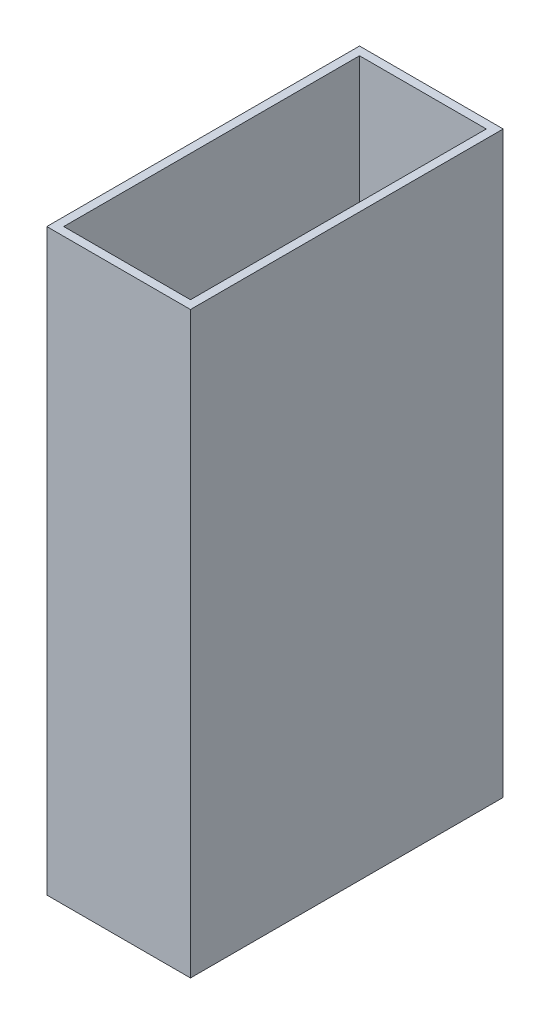
SolidWorks part; units mm, degrees
ref_plane "Plan de face" through (0, 0, 0) normal (0, 0, 1) x (1, 0, 0)
ref_plane "Plan de dessus" through (0, 0, 0) normal (0, 1, 0) x (1, 0, 0)
ref_plane "Plan de droite" through (0, 0, 0) normal (1, 0, 0) x (0, 0, -1)
sketch "Esquisse1" plane through (0, 0, 0) normal (0, 1, 0) x (1, 0, 0)
  line L0 (-17, 37) -> (17, 37)
  line L1 (-15, -35) -> (15, -35)
  line L2 (-15, -35) -> (-15, 35)
  line L3 (-15, 35) -> (15, 35)
  line L4 (15, -35) -> (15, 35)
  line L5 (-15, -35) -> (15, 35) construction
  line L6 (-15, 35) -> (15, -35) construction
  line L7 (17, -37) -> (17, 37)
  line L8 (-17, -37) -> (17, -37)
  line L9 (-17, -37) -> (-17, 37)
  point P0 (0, 0)
  dimension "D2" = 30
  dimension "D3" = 70
  dimension "D1" = 2
extrude "Boss.-Extru.1" add sketch "Esquisse1" along normal blind 135
extrude "Boss.-Extru.2" add sketch "Esquisse1<2>" against normal blind 2 contours L1 L4 L3 L2 | L9 L8 L7 L0 L4 L1 L2 L3 region at (0, 0, -36.1856) region at (0, 0, 0)
sketch "Esquisse1<2>" plane through (0, 0, 0) normal (0, 1, 0) x (1, 0, 0) same geometry as "Esquisse1"
